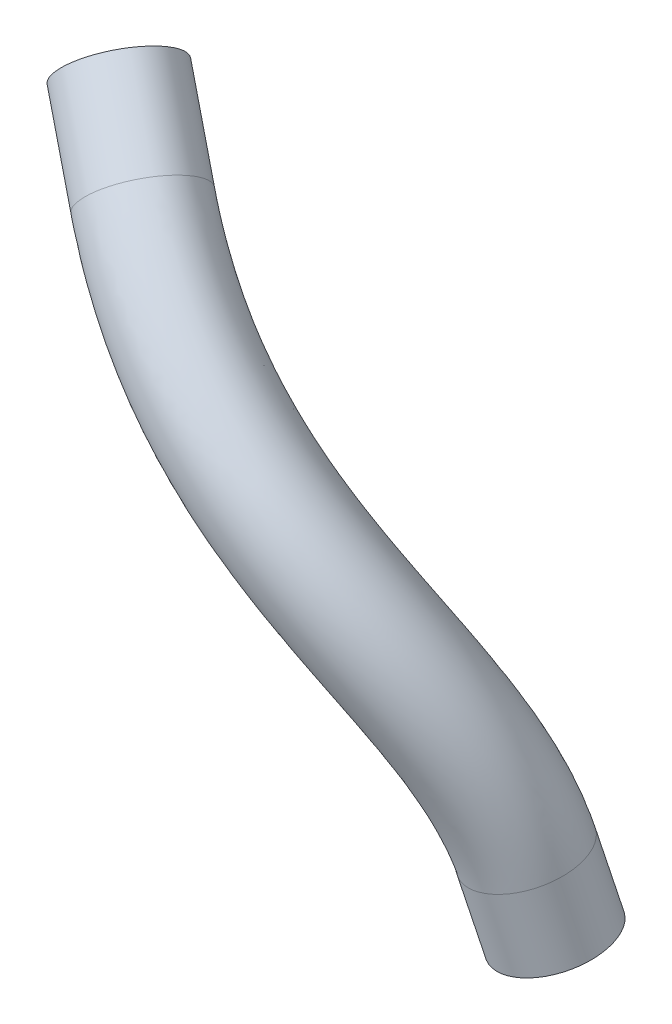
SolidWorks part; units mm, degrees
material "Silicon Rubber"
ref_plane "X-Y Datum" through (0, 0, 0) normal (0, 0, 1) x (1, 0, 0)
ref_plane "X-Z Datum" through (0, 0, 0) normal (0, 1, 0) x (1, 0, 0)
ref_plane "Y-Z Datum" through (0, 0, 0) normal (1, 0, 0) x (0, 0, -1)
sketch3d "3DSketch1"
  line L0 (27.5015, -11.1, -13.9429) -> (23.0956, 7.1738, -10.8516)
  line L1 (-71.5027, 110.3168, -5.1318) -> (-88.6777, 125.4988, -16.072)
  line L2 (-71.5027, 110.3168, -5.1318) -> (-88.6777, 125.4988, -16.072) construction
  line L3 (-88.6777, 125.4988, -16.072) -> (-76.1683, 114.441, -8.1038) construction
  line L4 (-88.6777, 125.4988, -16.072) -> (-34.1363, 77.2863, 18.6699) construction
  line L5 (23.0956, 7.1738, -10.8516) -> (24.827, -0.0072, -12.0664) construction
  circle A0 centre (-76.1683, 114.441, -8.1038) radius 9.5 construction
  circle A1 centre (-88.6777, 125.4988, -16.072) radius 9.5 construction
  circle A4 centre (-76.1683, 114.441, -8.1038) radius 9.5 construction
  circle A5 centre (-88.6777, 125.4988, -16.072) radius 9.5 construction
  circle A14 centre (23.0956, 7.1738, -10.8516) radius 9.525 construction
  circle A15 centre (24.827, -0.0072, -12.0664) radius 9.9344 construction
  circle A16 centre (23.0956, 7.1738, -10.8516) radius 9.525 construction
  circle A17 centre (24.827, -0.0072, -12.0664) radius 9.9344 construction
  spline S0 degree 3 poles (23.0956, 7.1738, -10.8516) (13.2611, 47.9635, -3.9512) (-24.9952, 69.2059, 24.4926) (-71.5027, 110.3168, -5.1318) knots 0 0 0 0 1 1 1 1
  point P8 (-82.5921, 120.1193, -12.1956)
  point P11 (-95.1014, 131.1771, -20.1638)
  point P13 (-82.5921, 120.1193, -12.1956)
  point P15 (20.8927, 16.3108, -9.3059)
  point P19 (22.5294, 9.5224, -10.4543)
  point P21 (20.8927, 16.3108, -9.3059)
  point P24 (22.5294, 9.5224, -10.4543)
  point P26 (-95.1014, 131.1771, -20.1638)
  dimension "D2" = 19.05
  dimension "D1" = 25.4
sweep "Sweep1" add path "3DSketch1" circular profile diameter 26.9875 parameters "D3"=26.9875
sweep "Cut-Sweep1" cut path "3DSketch1<2>" circular profile diameter 19.05 parameters "D3"=19.05
sketch3d "3DSketch1<2>" same geometry as "3DSketch1"
